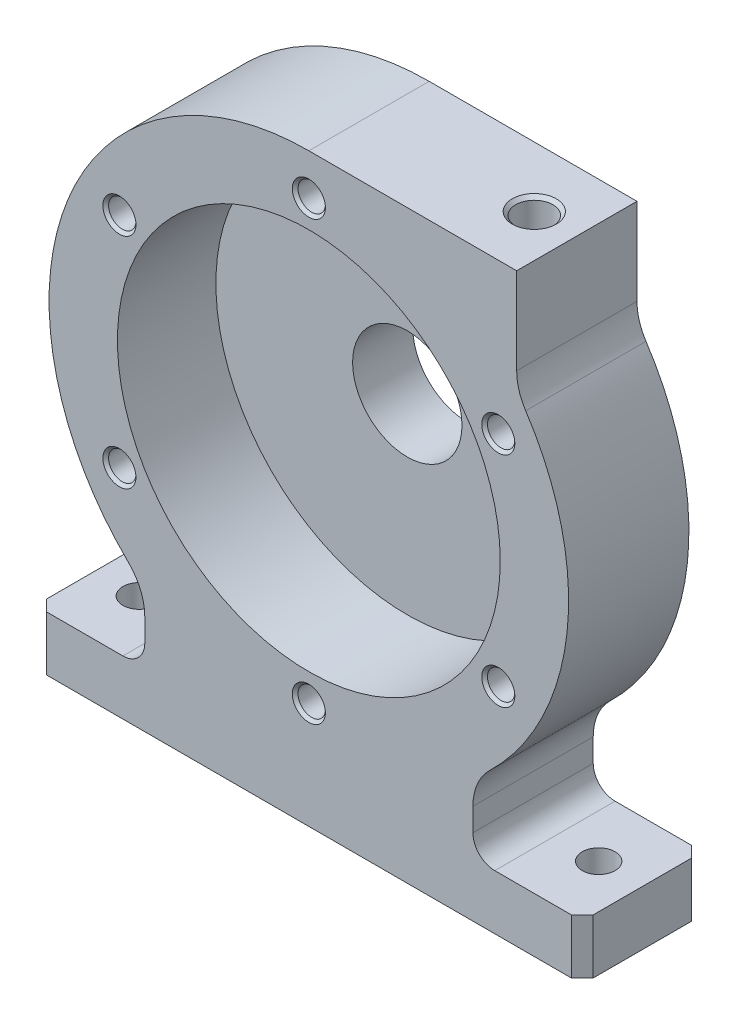
SolidWorks part; units mm, degrees
ref_plane "Front Plane" through (0, 0, 0) normal (0, 0, 1) x (1, 0, 0)
ref_plane "Top Plane" through (0, 0, 0) normal (0, 1, 0) x (1, 0, 0)
ref_plane "Right Plane" through (0, 0, 0) normal (1, 0, 0) x (0, 0, -1)
sketch "Sketch1" plane through (0, 0, 0) normal (0, 0, 1) x (1, 0, 0)
  line L0 (0, 0) -> (0, -59.5) construction
  line L1 (-50, -59.5) -> (50, -59.5)
  line L2 (50, -59.5) -> (50, -49.5)
  line L3 (50, -49.5) -> (34, -49.5)
  line L4 (30, -45.5) -> (30, -41.3068)
  line L5 (0, 47.5) -> (38, 47.5)
  line L6 (38, 47.5) -> (38, 31.6583)
  line L7 (-50, -59.5) -> (-50, -49.5)
  line L8 (-50, -49.5) -> (-34, -49.5)
  line L9 (-30, -45.5) -> (-30, -41.3068)
  arc A0 (0, 47.5) -> (-33.0435, -34.123) centre (0, 0) ccw
  arc A1 (33.0435, -34.123) -> (39.6522, 26.1525) centre (0, 0) ccw
  arc A2 (30, -41.3068) -> (33.0435, -34.123) centre (40, -41.3068) cw
  arc A3 (38, 31.6583) -> (39.6522, 26.1525) centre (48, 31.6583) ccw
  arc A4 (34, -49.5) -> (30, -45.5) centre (34, -45.5) cw
  arc A5 (-34, -49.5) -> (-30, -45.5) centre (-34, -45.5) ccw
  arc A6 (-30, -41.3068) -> (-33.0435, -34.123) centre (-40, -41.3068) ccw
  point P13 (30, -36.8273)
  dimension "D1" = 95
  dimension "D7" = 10
  dimension "D8" = 4
  dimension "D2" = 38
  dimension "D3" = 50
  dimension "D4" = 10
  dimension "D5" = 59.5
  dimension "D6" = 30
extrude "Boss-Extrude1" add sketch "Sketch1" along normal blind 22
sketch "Sketch2" plane through (0, 0, 22) normal (0, 0, 1) x (1, 0, 0)
  circle A0 centre (0, 0) radius 35
  dimension "D1" = 70
extrude "Cut-Extrude1" cut sketch "Sketch2" against normal blind 18
sketch "Sketch3" plane through (0, 0, 0) normal (0, 0, -1) x (-1, 0, 0)
  circle A0 centre (0, 0) radius 14
  dimension "D1" = 28
extrude "Boss-Extrude2" add sketch "Sketch3" along normal blind 7
fillet "Fillet1" radius 4 1 edges at (-14, 0, 0)
sketch "Sketch4" plane through (0, 0, -7) normal (0, 0, -1) x (-1, 0, 0)
  circle A0 centre (0, 0) radius 10
  dimension "D1" = 20
extrude "Cut-Extrude2" cut sketch "Sketch4" against normal through all
chamfer "Chamfer1" distance 2 angle 45 4 edges at (-50, -54.5, 0) (-50, -54.5, 22) (50, -54.5, 0) (50, -54.5, 22)
sketch "Sketch5" plane through (0, 47.5, 0) normal (0, 1, 0) x (1, 0, 0)
  line L0 (38, -11) -> (0, -11) construction
  line L1 (38, -22) -> (38, 0) construction
  line L2 (0, -22) -> (0, 0) construction
hole_wizard "M8x1.25 Tapped Hole1" positions "Sketch6" profile "Sketch7" tap size "M8x1.25" standard "ANSI Metric"
sketch "Sketch6" plane through (0, 47.5, 0) normal (0, 1, 0) x (1, 0, 0)
  line L0 (38, -11) -> (0, -11) construction
  line L1 (38, -22) -> (38, 0) construction
  point P0 (30.2242, -11)
  dimension "D1" = 7.7759
sketch "Sketch7" plane through (30.2242, 47.5, 11) normal (1, 0, 0) x (0, 0, 1)
  line L0 (0, 0) -> (0, 31.7929)
  line L1 (0, 31.7929) -> (3.4, 29.75)
  line L2 (3.4, 29.75) -> (3.4, 0.625)
  line L3 (3.4, 0.625) -> (4.025, 0)
  line L5 (4.025, 0) -> (0, 0)
  line L6 (-3.4, 0.625) -> (-4.025, 0) construction
  line L10 (0, 31.7929) -> (-3.4, 29.75) construction
  line L11 (0, -6.35) -> (0, 107.95) construction
  dimension "Tap Drill Dia." = 6.8
  dimension "Tap Drill Depth" = 29.75
  dimension "Near C'Sink Dia." = 8.05
  dimension "Near C'Sink Angle" = 90
  dimension "Drill Angle" = 118
cosmetic thread "Hole Thread1" parameters "D1"=16, "D2"=8
sketch "Sketch8" plane through (0, 0, 22) normal (0, 0, 1) x (1, 0, 0)
  circle A0 centre (0, 0) radius 40 construction
  dimension "D1" = 80
hole_wizard "M6x1.0 Tapped Hole1" positions "Sketch9" profile "Sketch10" tap size "M6x1.0" standard "ANSI Metric"
sketch "Sketch9" plane through (0, 0, 22) normal (0, 0, 1) x (1, 0, 0)
  circle A0 centre (0, 0) radius 40 construction
  point P0 (0, 40)
sketch "Sketch10" plane through (0, 40, 22) normal (1, 0, 0) x (0, -1, 0)
  line L0 (0, 0) -> (0, 16.5022)
  line L1 (0, 16.5022) -> (2.5, 15)
  line L2 (2.5, 15) -> (2.5, 0.525)
  line L3 (2.5, 0.525) -> (3.025, 0)
  line L5 (3.025, 0) -> (0, 0)
  line L6 (-2.5, 0.525) -> (-3.025, 0) construction
  line L10 (0, 16.5022) -> (-2.5, 15) construction
  line L11 (0, -6.35) -> (0, 107.95) construction
  dimension "Tap Drill Dia." = 5
  dimension "Tap Drill Depth" = 15
  dimension "Near C'Sink Dia." = 6.05
  dimension "Near C'Sink Angle" = 90
  dimension "Drill Angle" = 118
cosmetic thread "Hole Thread2" parameters "D1"=12, "D2"=6
pattern_circular "CirPattern1" count 6 over 360 about axis through (0, 0, 22) along (0, 0, -1) of "M6x1.0 Tapped Hole1"
hole_wizard "CSK for M8 Countersunk Flat Head Screw1" positions "Sketch11" profile "Sketch12" countersink size "M8" standard "ISO"
sketch "Sketch11" plane through (0, -59.5, 0) normal (0, -1, 0) x (-1, 0, 0)
  line L0 (-50, -20) -> (-50, -2) construction
  line L1 (50, -20) -> (50, -2) construction
  point P0 (42, -11)
  point P2 (-42, -11)
  point P10 (50, -11)
  point P11 (-50, -11)
  dimension "D1" = 8
  dimension "D2" = 8
sketch "Sketch12" plane through (-42, -59.5, 11) normal (1, 0, 0) x (0, 0, -1)
  line L0 (0, 0) -> (0, 21.8026)
  line L1 (0, 21.8026) -> (3, 20)
  line L2 (3, 20) -> (3, 1)
  line L3 (3, 1) -> (4, 0)
  line L5 (4, 0) -> (0, 0)
  line L6 (-3, 1) -> (-4, 0) construction
  line L10 (0, 21.8026) -> (-3, 20) construction
  line L11 (0, -6.35) -> (0, 107.95) construction
  dimension "Hole Dia." = 6
  dimension "Hole Depth" = 20
  dimension "Near C'Sink Dia." = 8
  dimension "Near C'Sink Angle" = 90
  dimension "Drill Angle" = 118
